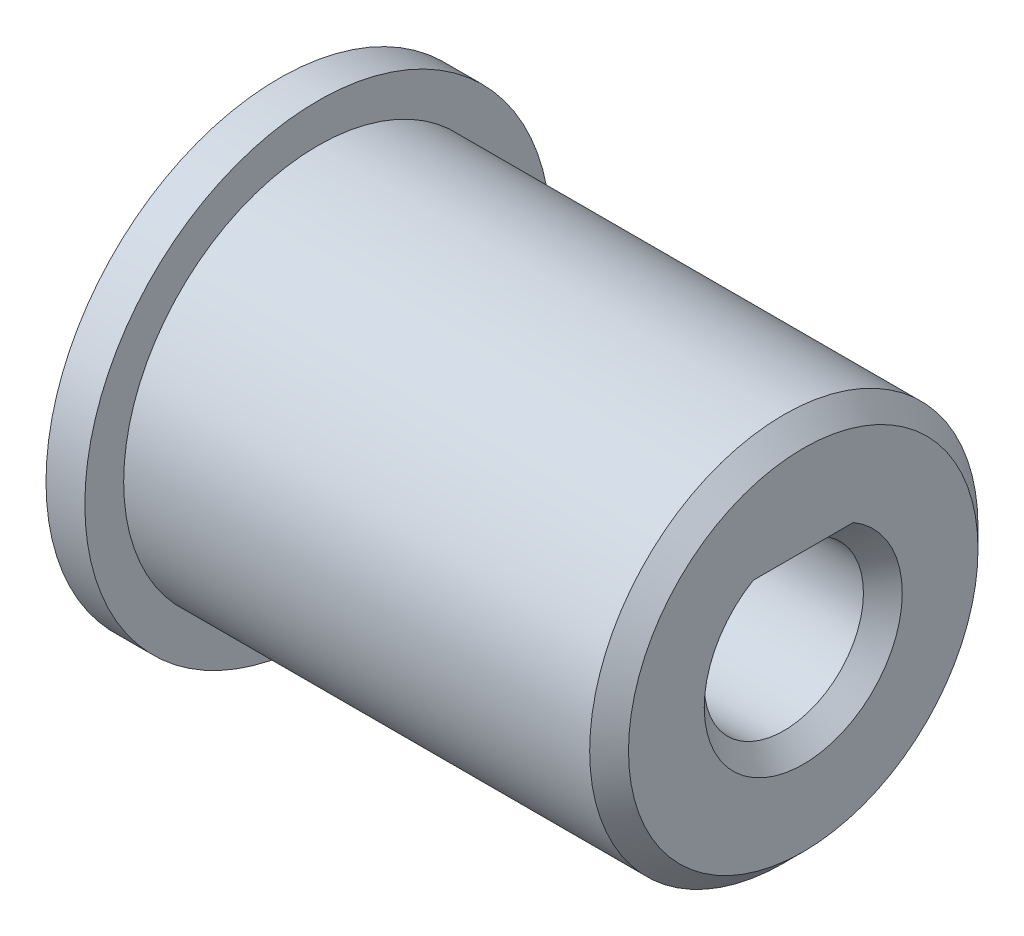
SolidWorks part; units mm, degrees
ref_plane "Ebene vorne" through (0, 0, 0) normal (0, 0, 1) x (1, 0, 0)
ref_plane "Ebene oben" through (0, 0, 0) normal (0, 1, 0) x (1, 0, 0)
ref_plane "Ebene rechts" through (0, 0, 0) normal (1, 0, 0) x (0, 0, -1)
sketch "Skizze2" plane through (0, 0, 0) normal (1, 0, 0) x (0, 0, -1)
  circle A0 centre (0, 0) radius 10
  dimension "D1" = 20
extrude "Aufsatz-Linear austragen1" add sketch "Skizze2" along normal blind 25
sketch "Skizze3" plane through (0, 0, 0) normal (-1, 0, 0) x (0, 0, 1)
  circle A0 centre (0, 0) radius 12
  dimension "D1" = 24
extrude "Aufsatz-Linear austragen2" add sketch "Skizze3" along normal blind 2
sketch "Skizze4" plane through (25, 0, 0) normal (1, 0, 0) x (0, 0, -1)
  line L0 (-2.2913, 3.4) -> (2.2913, 3.4)
  line L1 (-6.4521, 0) -> (8.6873, 0) construction
  arc A0 (-2.2913, 3.4) -> (2.2913, 3.4) centre (0, 0) ccw
  point P5 (0, -4.1)
  dimension "D1" = 4.1
  dimension "D2" = 7.5
extrude "Schnitt-Linear austragen1" cut sketch "Skizze4" against normal blind 15
chamfer "Fase1" distance 1 angle 45 2 edges at (25, 3.4, 0) (25, -4.1, 0)
chamfer "Fase2" distance 1 angle 45 1 edges at (25, 0, -10)
hole_wizard "Ø3.1 (3.1) Durchmesser Bohrung1" positions "Skizze5" profile "Skizze6" hole size "Ø3.1" standard "ISO"
sketch "Skizze5" plane through (-2, 0, 0) normal (-1, 0, 0) x (0, 0, 1)
  line L0 (0, 0) -> (-50000, 0) construction
  line L1 (0, 0) -> (0, -50000) construction
  point P5 (-4.25, 0)
  point P7 (4.25, 0)
  dimension "D1" = 8.5
sketch "Skizze6" plane through (-2, 0, 4.25) normal (0, 1, 0) x (0, 0, 1)
  line L0 (0, 0) -> (0, 7.9313)
  line L1 (0, 7.9313) -> (1.55, 7)
  line L2 (1.55, 7) -> (1.55, 0)
  line L5 (1.55, 0) -> (0, 0)
  line L10 (0, 7.9313) -> (-1.55, 7) construction
  line L11 (0, -6.35) -> (0, 107.95) construction
  dimension "Bohrerdurchmesser" = 3.1
  dimension "Bohrungstiefe" = 7
  dimension "Spitzenwinkel" = 118
chamfer "Fase3" distance 1 angle 45 2 edges at (-2, 0, 5.8) (-2, 0, -2.7)
